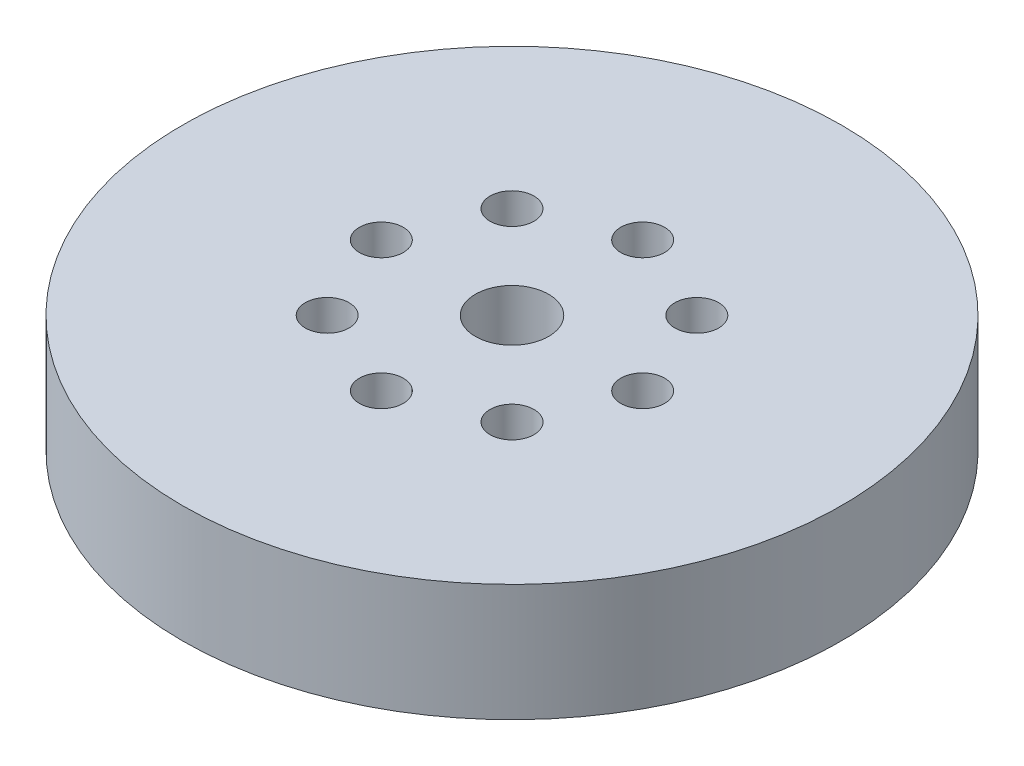
SolidWorks part; units mm, degrees
ref_plane "Front Plane" through (0, 0, 0) normal (0, 0, 1) x (1, 0, 0)
ref_plane "Top Plane" through (0, 0, 0) normal (0, 1, 0) x (1, 0, 0)
ref_plane "Right Plane" through (0, 0, 0) normal (1, 0, 0) x (0, 0, -1)
sketch "Sketch1" plane through (0, 0, 0) normal (0, 1, 0) x (1, 0, 0)
  circle A0 centre (0, 0) radius 45
  dimension "FLANGE_OD" = 90
extrude "Boss-Extrude1" add sketch "Sketch1" along normal blind 16
sketch "Sketch2" plane through (0, 0, 0) normal (0, 1, 0) x (1, 0, 0)
  circle A0 centre (0, 0) radius 5
  dimension "BORE_D" = 10
extrude "Cut-Extrude1" cut sketch "Sketch2" along normal through all
sketch "Sketch3" plane through (0, 16, 0) normal (0, 1, 0) x (1, 0, 0)
  circle A0 centre (0, 0) radius 17.8444 construction
  circle A1 centre (-17.8444, 0) radius 2.9949
  dimension "BOLT_D" = 5.9898
  dimension "BOLT_PCD" = 35.6888
extrude "Cut-Extrude2" cut sketch "Sketch3" against normal blind 10.1115
pattern_circular "CirPattern1" count 8 over 360 about axis through (0, 0, 0) along (0, 1, 0) of "Cut-Extrude2"
